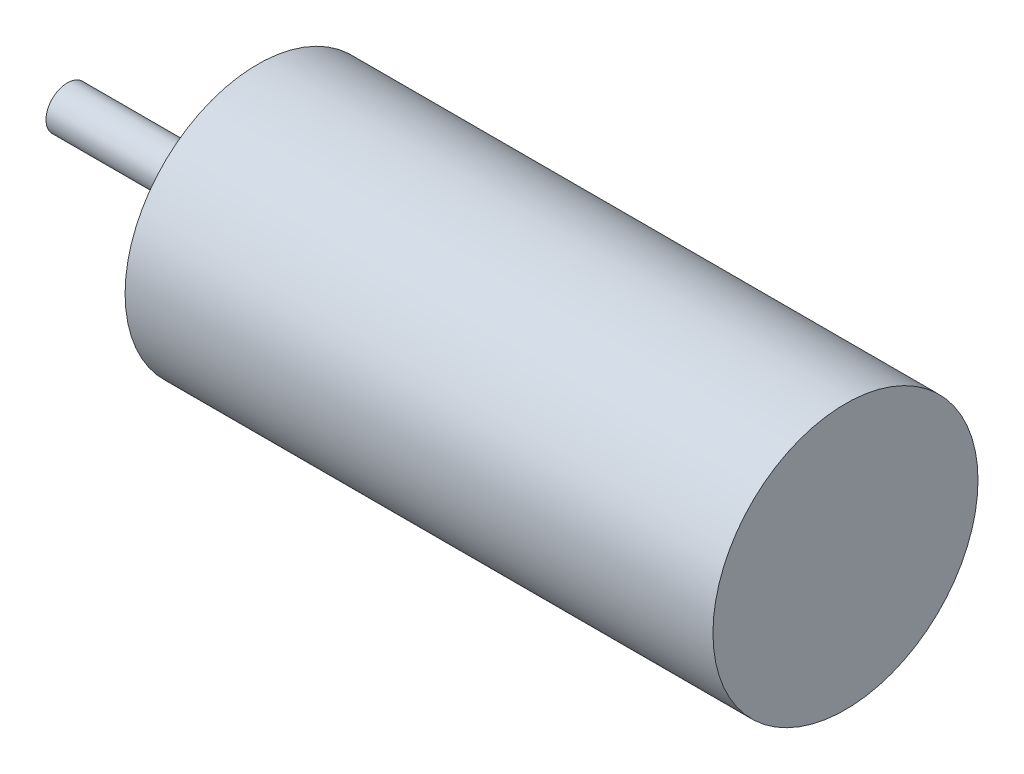
SolidWorks part; units mm, degrees
ref_plane "Front Plane" through (0, 0, 0) normal (0, 0, 1) x (1, 0, 0)
ref_plane "Top Plane" through (0, 0, 0) normal (0, 1, 0) x (1, 0, 0)
ref_plane "Right Plane" through (0, 0, 0) normal (1, 0, 0) x (0, 0, -1)
sketch "Sketch1" plane through (0, 0, 0) normal (0, 0, 1) x (1, 0, 0)
  line L0 (0, 0) -> (72.8, 0)
  line L1 (0, 0) -> (0, 2)
  line L2 (0, 2) -> (15.5, 2)
  line L3 (15.5, 2) -> (15.5, 4)
  line L4 (15.5, 4) -> (17.8, 4)
  line L5 (17.8, 4) -> (17.8, 12.4)
  line L6 (17.8, 12.4) -> (72.8, 12.4)
  line L7 (72.8, 12.4) -> (72.8, 0)
  dimension "D1" = 72.8
  dimension "D2" = 2
  dimension "D3" = 4
  dimension "D4" = 12.4
  dimension "D5" = 55
  dimension "D6" = 15.5
revolve "Revolve1" add sketch "Sketch1" angle 360 about L0
sketch "Sketch2" plane through (17.8, 0, 0) normal (-1, 0, 0) x (0, 0, 1)
  line L0 (0, 8.5) -> (0, -8.5) construction
  circle A0 centre (0, 8.5) radius 1.5
  circle A1 centre (0, -8.5) radius 1.5
  dimension "D1" = 17
  dimension "D2" = 3
extrude "Cut-Extrude1" cut sketch "Sketch2" against normal blind 5
